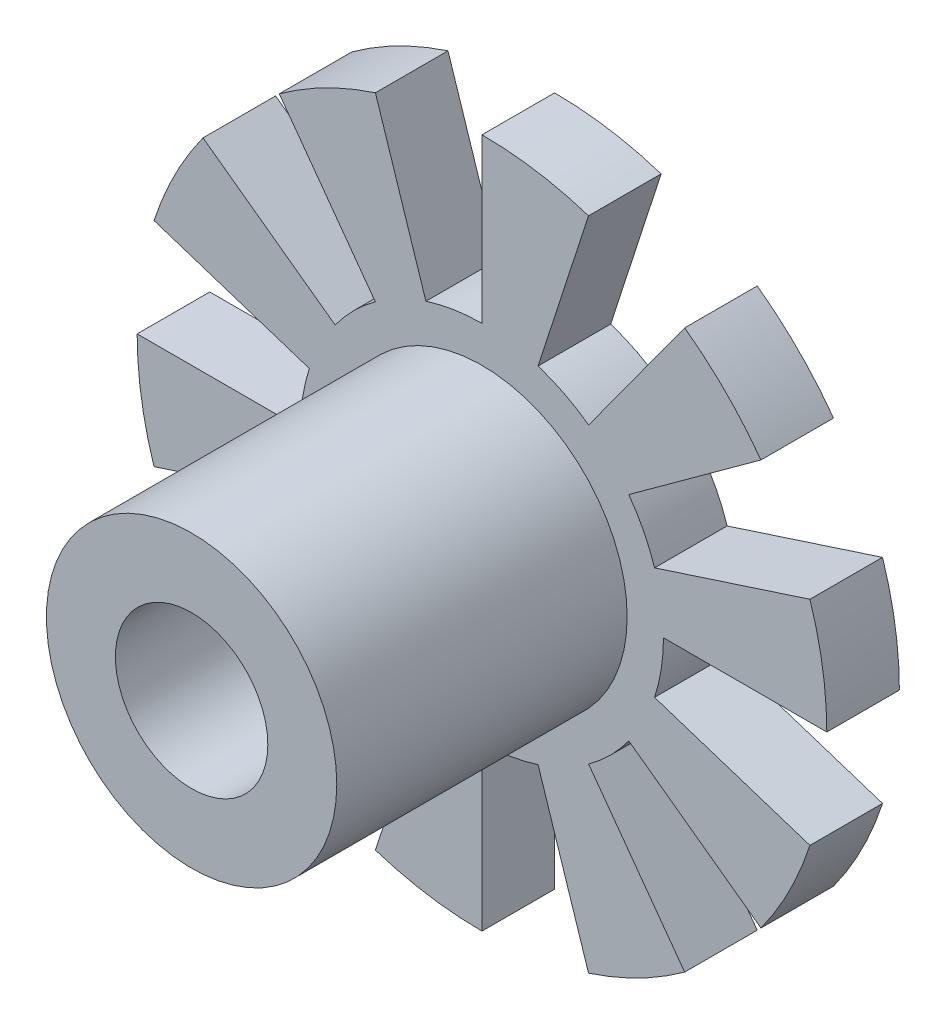
SolidWorks part; units mm, degrees
ref_plane "Plan de face" through (0, 0, 0) normal (0, 0, 1) x (1, 0, 0)
ref_plane "Plan de dessus" through (0, 0, 0) normal (0, 1, 0) x (1, 0, 0)
ref_plane "Plan de droite" through (0, 0, 0) normal (1, 0, 0) x (0, 0, -1)
sketch "Esquisse1" plane through (0, 0, 0) normal (0, 0, 1) x (1, 0, 0)
  line L0 (0, 5) -> (0, 9.5)
  line L1 (1.5451, 4.7553) -> (2.9357, 9.035)
  line L2 (2.9389, 4.0451) -> (5.584, 7.6857)
  line L3 (4.0451, 2.9389) -> (7.6857, 5.584)
  line L4 (4.7553, 1.5451) -> (9.035, 2.9357)
  line L5 (5, 0) -> (9.5, 0)
  line L6 (4.7553, -1.5451) -> (9.035, -2.9357)
  line L7 (4.0451, -2.9389) -> (7.6857, -5.584)
  line L8 (2.9389, -4.0451) -> (5.584, -7.6857)
  line L9 (1.5451, -4.7553) -> (2.9357, -9.035)
  line L10 (0, -5) -> (0, -9.5)
  line L11 (-1.5451, -4.7553) -> (-2.9357, -9.035)
  line L12 (-2.9389, -4.0451) -> (-5.584, -7.6857)
  line L13 (-4.0451, -2.9389) -> (-7.6857, -5.584)
  line L14 (-4.7553, -1.5451) -> (-9.035, -2.9357)
  line L15 (-5, 0) -> (-9.5, 0)
  line L16 (-4.7553, 1.5451) -> (-9.035, 2.9357)
  line L17 (-4.0451, 2.9389) -> (-7.6857, 5.584)
  line L18 (-2.9389, 4.0451) -> (-5.584, 7.6857)
  line L19 (-1.5451, 4.7553) -> (-2.9357, 9.035)
  arc A0 (-7.6857, 5.584) -> (-9.035, 2.9357) centre (0, 0) ccw
  circle A1 centre (0, 0) radius 2.1
  circle A2 centre (0, 0) radius 4
  arc A4 (-2.9389, 4.0451) -> (-4.0451, 2.9389) centre (0, 0) ccw
  arc A5 (-2.9357, 9.035) -> (-5.584, 7.6857) centre (0, 0) ccw
  arc A6 (2.9357, 9.035) -> (0, 9.5) centre (0, 0) ccw
  arc A7 (2.9389, 4.0451) -> (1.5451, 4.7553) centre (0, 0) ccw
  arc A8 (7.6857, 5.584) -> (5.584, 7.6857) centre (0, 0) ccw
  arc A9 (4.7553, 1.5451) -> (4.0451, 2.9389) centre (0, 0) ccw
  arc A10 (9.5, 0) -> (9.035, 2.9357) centre (0, 0) ccw
  arc A11 (4.7553, -1.5451) -> (5, 0) centre (0, 0) ccw
  arc A12 (7.6857, -5.584) -> (9.035, -2.9357) centre (0, 0) ccw
  arc A13 (2.9357, -9.035) -> (5.584, -7.6857) centre (0, 0) ccw
  arc A14 (-2.9357, -9.035) -> (0, -9.5) centre (0, 0) ccw
  arc A15 (-7.6857, -5.584) -> (-5.584, -7.6857) centre (0, 0) ccw
  arc A16 (-9.5, 0) -> (-9.035, -2.9357) centre (0, 0) ccw
  arc A17 (-4.7553, 1.5451) -> (-5, 0) centre (0, 0) ccw
  arc A18 (-4.7553, -1.5451) -> (-4.0451, -2.9389) centre (0, 0) ccw
  arc A19 (-2.9389, -4.0451) -> (-1.5451, -4.7553) centre (0, 0) ccw
  arc A20 (0, -5) -> (1.5451, -4.7553) centre (0, 0) ccw
  arc A21 (2.9389, -4.0451) -> (4.0451, -2.9389) centre (0, 0) ccw
  arc A22 (0, 5) -> (-1.5451, 4.7553) centre (0, 0) ccw
  point P1 (0, 0)
  point P49 (0, 0)
  dimension "D1" = 19
  dimension "D2" = 8
  dimension "D3" = 1
  dimension "D4" = 20
  dimension "D5" = 4.2
extrude "Boss.-Extru.3" add sketch "Esquisse1" along normal blind 2 contours L0 A22 L19 A5 L18 A4 L17 A0 L16 A17 L15 A16 L14 A18 L13 A15 L12 A19 L11 A14 L10 A20 L9 A13 L8 A21 L7 A12 L6 A11 L5 A10 L4 A9 L3 A8 L2 A7 L1 A6 A2 | A2 A1 region at (0.2687, 7.25, 0) region at (-3.8869, 0, 0)
extrude "Boss.-Extru.4" add sketch "Esquisse1<3>" along normal blind 10 contours A2 | A1
sketch "Esquisse1<3>" plane through (0, 0, 0) normal (0, 0, 1) x (1, 0, 0) same geometry as "Esquisse1"
